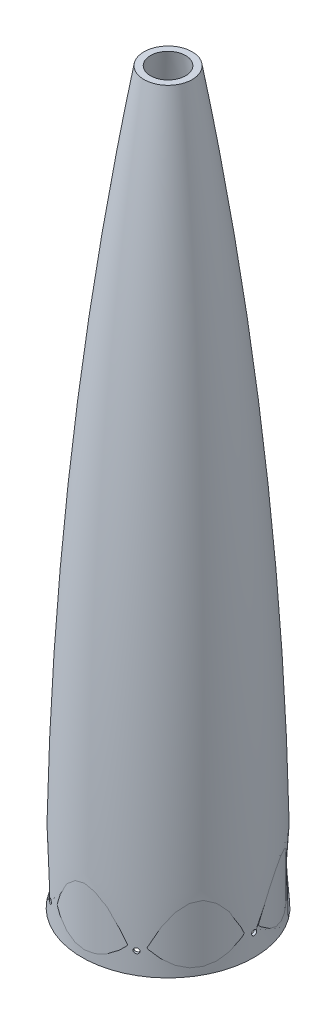
SolidWorks part; units mm, degrees
ref_plane "Front Plane" through (0, 0, 0) normal (0, 0, 1) x (1, 0, 0)
ref_plane "Top Plane" through (0, 0, 0) normal (0, 1, 0) x (1, 0, 0)
ref_plane "Right Plane" through (0, 0, 0) normal (1, 0, 0) x (0, 0, -1)
sketch "Sketch2" plane through (0, 0, 0) normal (0, 0, 1) x (1, 0, 0)
  line L0 (0, 0) -> (0, 622.8612) construction
  line L1 (-530.0058, 0) -> (530.0058, 0) construction
  line L2 (0, 0) -> (-51.054, 0)
  line L3 (0, 0) -> (51.054, 0)
  line L4 (0, 508) -> (0, 0)
  arc A0 (-51.054, 0) -> (0, 508) centre (2501.8362, 0) cw
  point P6 (0, 0)
  dimension "D1" = 102.108
  dimension "D2" = 508
  dimension "D3" = 51.054
revolve "Revolve1" add sketch "Sketch2" angle 360 about L0 region at (-20.4392, 190.7566, 0)
shell "Shell2" thickness 3.81 removed face at (0, 0, -51.054)
sketch "Sketch4" plane through (0, 0, 0) normal (1, 0, 0) x (0, 0, -1)
  line L0 (0, 508) -> (0, 431.8) construction
  line L1 (0, 431.8) -> (38.8012, 431.8) construction
  line L3 (38.8012, 431.8) -> (-44.732, 431.8)
  line L4 (38.8012, 431.8) -> (38.8012, 549.0104)
  line L5 (38.8012, 549.0104) -> (-44.732, 549.0104)
  line L6 (-44.732, 431.8) -> (-44.732, 549.0104)
  dimension "D1" = 117.2104
  dimension "D2" = 83.5332
  dimension "D3" = 38.8012
  dimension "D4" = 76.2
extrude "Cut-Extrude2" cut sketch "Sketch4" against normal mid plane 174.752
sketch "Sketch5" plane through (0, 0, 0) normal (0, -1, 0) x (1, 0, 0)
  circle A0 centre (0, 0) radius 49.53
extrude "Cut-Extrude5" cut sketch "Sketch5" against normal blind 80.01
sketch "Sketch6" plane through (0, 0, 0) normal (1, 0, 0) x (0, 0, -1)
  line L0 (0, 0) -> (0, 12.7) construction
  circle A0 centre (0, 12.7) radius 1.524
  dimension "D2" = 3.048
  dimension "D1" = 12.7
extrude "Cut-Extrude6" cut sketch "Sketch6" against normal blind 62.484 contours A0 | A0 region at (0, 12.7, 0)
pattern_circular "CirPattern1" count 6 over 360 about axis through (0, 80.01, 0) along (0, -1, 0) of "Cut-Extrude6" reverse direction yes
